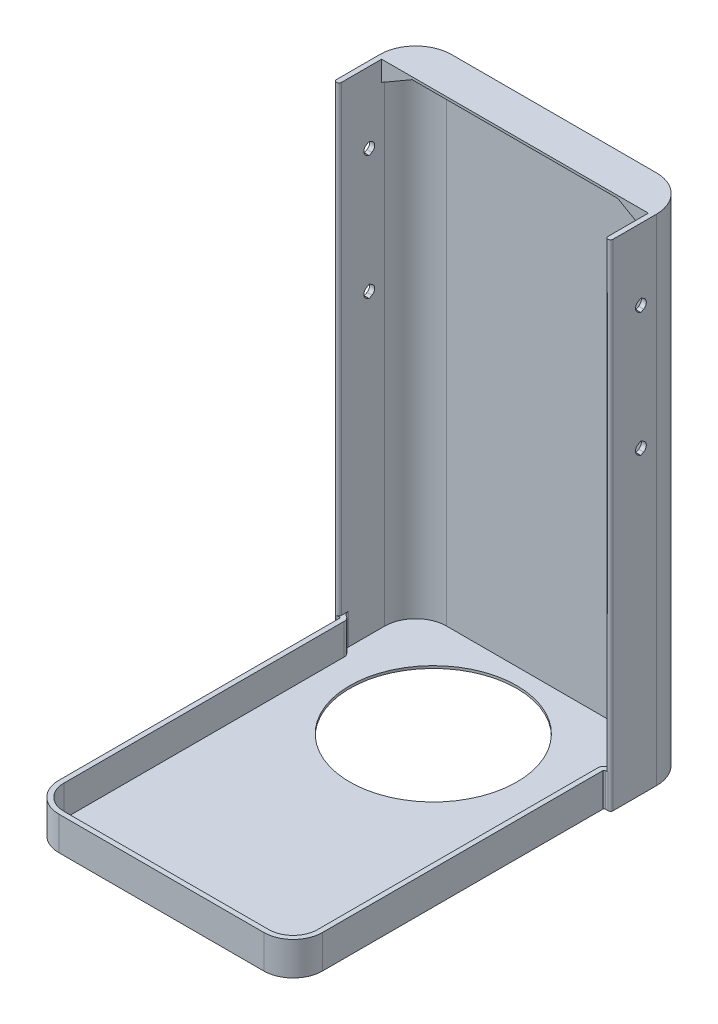
SolidWorks part; units mm, degrees
material "ABS"
ref_plane "Front Plane" through (0, 0, 0) normal (0, 0, 1) x (1, 0, 0)
ref_plane "Top Plane" through (0, 0, 0) normal (0, 1, 0) x (1, 0, 0)
ref_plane "Right Plane" through (0, 0, 0) normal (1, 0, 0) x (0, 0, -1)
sketch "Sketch1" plane through (0, 0, 0) normal (0, 1, 0) x (1, 0, 0)
  line L0 (-33.1, 0) -> (33.1, 0)
  line L1 (-43.1, -10) -> (-43.1, -24)
  line L2 (43.1, -10) -> (43.1, -24)
  line L5 (-43.1, -16.5) -> (43.1, -16.5) construction
  line L6 (-43.1, -13.5) -> (43.1, -13.5) construction
  line L7 (0, -13.5) -> (0, -16.5) construction
  line L9 (44.7, -10) -> (44.7, -24)
  line L10 (-33.1, 1.6) -> (33.1, 1.6)
  line L11 (-44.7, -10) -> (-44.7, -24)
  line L13 (0, -15) -> (0, -11) construction
  line L14 (0, -15) -> (0, -19) construction
  line L15 (44.7, -29) -> (44.7, -45) construction
  line L16 (46.3, -29) -> (46.3, -45) construction
  line L17 (-47.7853, -29.1701) -> (-46.5109, -45.0161) construction
  line L18 (-46.1905, -29.0418) -> (-44.9161, -44.8878) construction
  arc A2 (-33.1, 0) -> (-43.1, -10) centre (-33.1, -10) ccw
  arc A3 (43.1, -10) -> (33.1, 0) centre (33.1, -10) ccw
  arc A8 (44.7, -10) -> (33.1, 1.6) centre (33.1, -10) ccw
  arc A9 (-33.1, 1.6) -> (-44.7, -10) centre (-33.1, -10) ccw
  arc A14 (44.6016, -30.7729) -> (44.7, -29) centre (28.675, -29) cw construction
  arc A15 (46.2377, -30.4806) -> (46.3, -29) centre (28.675, -29) cw construction
  arc A16 (44.7, -24) -> (46.2377, -30.4806) centre (59.125, -24) ccw construction
  arc A17 (43.1, -24) -> (44.6016, -30.7729) centre (59.125, -24) ccw construction
  arc A18 (-43.1, -24) -> (-45.5924, -32.3158) centre (-58.2187, -24) cw construction
  arc A19 (-44.7, -24) -> (-47.3288, -32.0103) centre (-58.2187, -24) cw construction
  arc A20 (-47.3288, -32.0103) -> (-47.7853, -29.1701) centre (-29.644, -27.7111) ccw construction
  arc A21 (-45.5924, -32.3158) -> (-46.1905, -29.0418) centre (-29.644, -27.7111) ccw construction
  arc A22 (-44.7, -24) -> (-43.1, -24) centre (-43.9, -24) ccw
  arc A23 (43.1, -24) -> (44.7, -24) centre (43.9, -24) ccw
  point P25 (0, -15)
  dimension "D3" = 10
  dimension "D1" = 1.6
  dimension "D2" = 86.2
  dimension "D4" = 9
  dimension "D5" = 4
  dimension "D6" = 3
  dimension "D7" = 15
extrude "Boss-Extrude1" add sketch "Sketch1" along normal blind 160
sketch "Sketch2" plane through (0, 160, 0) normal (0, 1, 0) x (1, 0, 0)
  line L0 (44.7, -10) -> (44.7, -24) construction
  line L1 (-33.1, 1.6) -> (33.1, 1.6) construction
  line L2 (-44.7, -10) -> (-44.7, -24) construction
  line L3 (44.7, -10) -> (44.7, -11)
  line L4 (-33.1, 1.6) -> (33.1, 1.6)
  line L5 (-44.7, -10) -> (-44.7, -11)
  line L6 (-44.7, -11) -> (44.7, -11)
  arc A0 (44.7, -10) -> (33.1, 1.6) centre (33.1, -10) ccw construction
  arc A1 (-33.1, 1.6) -> (-44.7, -10) centre (-33.1, -10) ccw construction
  arc A2 (44.7, -10) -> (33.1, 1.6) centre (33.1, -10) ccw
  arc A3 (-33.1, 1.6) -> (-44.7, -10) centre (-33.1, -10) ccw
extrude "Boss-Extrude2" add sketch "Sketch2" against normal blind 0.8
sketch "Sketch3" plane through (44.7, 0, 0) normal (1, 0, 0) x (0, 0, -1)
  line L0 (-19, 160) -> (-11, 160) construction
  line L1 (-24, 160) -> (-10, 160) construction
  line L2 (-15, 160) -> (-15, 137) construction
  line L3 (-15, 137) -> (-15, 97) construction
  line L4 (-15.875, 138.5155) -> (-15, 139.0207)
  line L5 (-15, 139.0207) -> (-14.125, 138.5155)
  line L6 (-15.875, 135.4845) -> (-15, 134.9793)
  line L7 (-15, 134.9793) -> (-14.125, 135.4845)
  line L8 (-15.875, 98.5155) -> (-15, 99.0207)
  line L9 (-15, 99.0207) -> (-14.125, 98.5155)
  line L10 (-14.125, 95.4845) -> (-15, 94.9793)
  line L11 (-15, 94.9793) -> (-15.875, 95.4845)
  arc A0 (-15.875, 138.5155) -> (-15.875, 135.4845) centre (-15, 137) ccw
  arc A1 (-14.125, 135.4845) -> (-14.125, 138.5155) centre (-15, 137) ccw
  arc A2 (-15.875, 98.5155) -> (-15.875, 95.4845) centre (-15, 97) ccw
  arc A3 (-14.125, 95.4845) -> (-14.125, 98.5155) centre (-15, 97) ccw
  dimension "D2" = 1.75
  dimension "D1" = 120
  dimension "D3" = 23
  dimension "D4" = 40
  dimension "D5" = 8
extrude "Cut-Extrude1" cut sketch "Sketch3" against normal through all
sketch "Sketch4" plane through (0, 0, 0) normal (0, -1, 0) x (1, 0, 0)
  line L0 (-43.9, 24.8) -> (-42.6, 24.8)
  line L1 (-42.6, 24.8) -> (-42.6, 115.8)
  line L2 (-33.1, 125.3) -> (33.1, 125.3)
  line L3 (-43.1, 115.8) -> (-43.1, 46.8) construction
  line L5 (42.6, 115.8) -> (42.6, 24.8)
  line L6 (42.6, 24.8) -> (43.9, 24.8)
  line L7 (-43.1, 24) -> (-43.1, 10) construction
  line L8 (-33.1, 0) -> (33.1, 0) construction
  line L9 (43.1, 10) -> (43.1, 24) construction
  line L10 (-43.1, 24) -> (-43.1, 10)
  line L11 (-33.1, 0) -> (33.1, 0)
  line L12 (43.1, 10) -> (43.1, 24)
  arc A0 (-43.1, 24) -> (-44.7, 24) centre (-43.9, 24) ccw construction
  arc A1 (-42.6, 115.8) -> (-33.1, 125.3) centre (-33.1, 115.8) cw
  arc A2 (-33.1, 125.8) -> (-43.1, 115.8) centre (-33.1, 115.8) ccw construction
  arc A3 (33.1, 125.3) -> (42.6, 115.8) centre (33.1, 115.8) cw
  arc A4 (43.1, 115.8) -> (33.1, 125.8) centre (33.1, 115.8) ccw construction
  arc A5 (44.7, 24) -> (43.1, 24) centre (43.9, 24) ccw construction
  arc A6 (-43.1, 10) -> (-33.1, 0) centre (-33.1, 10) ccw construction
  arc A7 (33.1, 0) -> (43.1, 10) centre (33.1, 10) ccw construction
  arc A8 (43.9, 24.8) -> (43.1, 24) centre (43.9, 24) ccw
  arc A9 (-43.1, 24) -> (-43.9, 24.8) centre (-43.9, 24) ccw
  arc A10 (-43.1, 10) -> (-33.1, 0) centre (-33.1, 10) ccw
  arc A11 (33.1, 0) -> (43.1, 10) centre (33.1, 10) ccw
  circle A12 centre (-5.1, 32.3) radius 25 construction
  circle A13 centre (-5.1, 32.3) radius 25 construction
  circle A14 centre (-5.1, 32.3) radius 27
  point P19 (42.6, 24.8)
  dimension "D1" = 0.5
  dimension "D2" = 2
extrude "Boss-Extrude3" add sketch "Sketch4" against normal blind 0.8
fillet "Fillet1" radius 0.4 2 edges at (42.6, 0.4, 24.8) (-42.6, 0.4, 24.8)
sketch "Sketch6" plane through (0, 0.8, 0) normal (0, 1, 0) x (1, 0, 0)
  line L0 (-43.1, -23.2) -> (-43, -23.2)
  line L1 (-43.1, -24) -> (-43.1, -11) construction
  line L2 (-41, -25.2) -> (-41, -115.8)
  line L3 (-33.1, -123.7) -> (33.1, -123.7)
  line L4 (41, -115.8) -> (41, -25.2)
  line L5 (43, -23.2) -> (43.1, -23.2)
  line L6 (43.1, -11) -> (43.1, -24) construction
  line L7 (41, -25.2) -> (42.6, -25.2) construction
  line L8 (43.1, -23.2) -> (44.7, -23.2) construction
  line L9 (44.7, -24) -> (44.7, -10) construction
  line L10 (-43, -24.8) -> (-43.9, -24.8) construction
  line L13 (-43.1, -24) -> (-43.1, -10) construction
  line L15 (-42.6, -115.8) -> (-42.6, -25.2) construction
  line L18 (43.1, -10) -> (43.1, -24) construction
  line L19 (43.9, -24.8) -> (43, -24.8) construction
  line L20 (42.6, -25.2) -> (42.6, -115.8) construction
  line L21 (33.1, -125.3) -> (-33.1, -125.3) construction
  line L22 (43.1, -23.2) -> (43.1, -24)
  line L23 (43.9, -24.8) -> (43, -24.8)
  line L24 (42.6, -25.2) -> (42.6, -115.8)
  line L25 (33.1, -125.3) -> (-33.1, -125.3)
  line L26 (-42.6, -115.8) -> (-42.6, -25.2)
  line L27 (-43, -24.8) -> (-43.9, -24.8)
  line L28 (-43.1, -24) -> (-43.1, -23.2)
  arc A0 (-43, -23.2) -> (-41, -25.2) centre (-43, -25.2) cw
  arc A1 (-41, -115.8) -> (-33.1, -123.7) centre (-33.1, -115.8) ccw
  arc A2 (33.1, -123.7) -> (41, -115.8) centre (33.1, -115.8) ccw
  arc A3 (41, -25.2) -> (43, -23.2) centre (43, -25.2) cw
  arc A4 (43, -24.8) -> (42.6, -25.2) centre (43, -25.2) ccw construction
  arc A5 (-42.6, -115.8) -> (-33.1, -125.3) centre (-33.1, -115.8) ccw construction
  arc A6 (33.1, -125.3) -> (42.6, -115.8) centre (33.1, -115.8) ccw construction
  arc A7 (-42.6, -25.2) -> (-43, -24.8) centre (-43, -25.2) ccw construction
  arc A9 (-43.9, -24.8) -> (-43.1, -24) centre (-43.9, -24) ccw construction
  arc A15 (43.1, -24) -> (43.9, -24.8) centre (43.9, -24) ccw construction
  arc A16 (43.1, -24) -> (43.9, -24.8) centre (43.9, -24) ccw
  arc A17 (43, -24.8) -> (42.6, -25.2) centre (43, -25.2) ccw
  arc A18 (33.1, -125.3) -> (42.6, -115.8) centre (33.1, -115.8) ccw
  arc A19 (-42.6, -115.8) -> (-33.1, -125.3) centre (-33.1, -115.8) ccw
  arc A20 (-42.6, -25.2) -> (-43, -24.8) centre (-43, -25.2) ccw
  arc A21 (-43.9, -24.8) -> (-43.1, -24) centre (-43.9, -24) ccw
  point P32 (-41.9964, -22.8777)
extrude "Boss-Extrude4" add sketch "Sketch6" along normal blind 10
fillet "Fillet2" radius 2 2 edges at (43.1, 5.8, 23.2) (-43.1, 5.8, 23.2)
chamfer "Chamfer1" distance 5.7 angle 60 5 edges at (-43.1, 159.2, 10.5) (43.1, 159.2, 10.5) (-40.1711, 159.2, 2.9289) (40.1711, 159.2, 2.9289) (0, 159.2, 0) first distance on face at (-43.1, 137, 15) first distance on face at (43.1, 137, 15) first distance on face at (-39.1355, 80, 3.9645) first distance on face at (39.1355, 80, 3.9645) first distance on face at (0, 80, 0)
